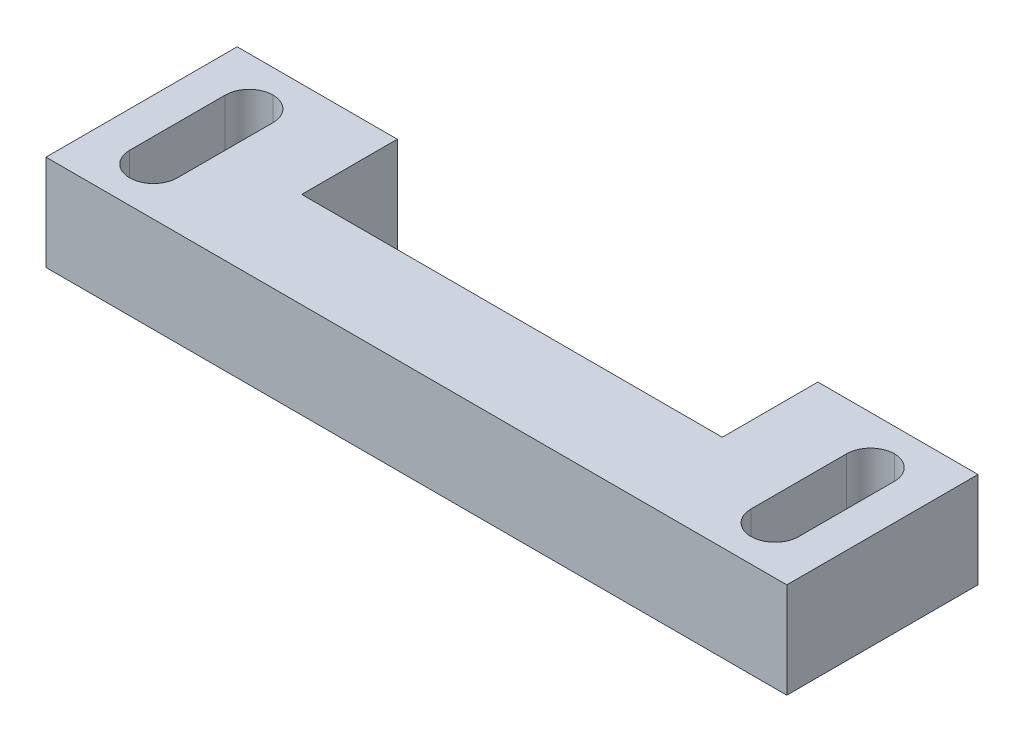
SolidWorks part; units mm, degrees
material "6061 Alloy"
ref_plane "Front Plane" through (0, 0, 0) normal (0, 0, 1) x (1, 0, 0)
ref_plane "Top Plane" through (0, 0, 0) normal (0, 1, 0) x (1, 0, 0)
ref_plane "Right Plane" through (0, 0, 0) normal (1, 0, 0) x (0, 0, -1)
sketch "Sketch1" plane through (0, 0, 0) normal (0, 0, 1) x (1, 0, 0)
  line L1 (-49.2125, 6.35) -> (49.2125, 6.35)
  line L2 (-49.2125, 6.35) -> (-49.2125, -6.35)
  line L3 (-49.2125, -6.35) -> (49.2125, -6.35)
  line L4 (49.2125, 6.35) -> (49.2125, -6.35)
  dimension "D1" = 49.2125
  dimension "D2" = 49.2125
  dimension "D3" = 6.35
  dimension "D4" = 6.35
extrude "Boss-Extrude1" add sketch "Sketch1" along normal mid plane 25.4
sketch "Sketch2" plane through (0, 6.35, 0) normal (0, 1, 0) x (1, 0, 0)
  line L1 (-44.45, 9.525) -> (-38.1, 9.525)
  line L2 (-44.45, 9.525) -> (-44.45, -9.525)
  line L3 (-44.45, -9.525) -> (-38.1, -9.525)
  line L4 (-38.1, 9.525) -> (-38.1, -9.525)
  line L5 (49.2125, 12.7) -> (-49.2125, 12.7) construction
  line L6 (49.2125, -12.7) -> (-49.2125, -12.7) construction
  dimension "D1" = 38.1
  dimension "D2" = 6.35
  dimension "D3" = 3.175
  dimension "D4" = 3.175
extrude "Cut-Extrude1" cut sketch "Sketch2" against normal up to next
fillet "Fillet1" radius 3.175 1 edges at (-44.45, 0, -9.525) type face fillet first side face at (-44.45, 0, 0) second side face at (-41.275, 0, -9.525)
fillet "Fillet2" radius 3.175 1 edges at (-38.1, 0, -9.525) type face fillet first side face at (-39.6875, 0, -9.525) second side face at (-38.1, 0, 0)
fillet "Fillet3" radius 3.175 1 edges at (-44.45, 0, 9.525) type face fillet first side face at (-44.45, 0, 1.5875) second side face at (-41.275, 0, 9.525)
fillet "Fillet4" radius 3.175 1 edges at (-38.1, 0, 9.525) type face fillet first side face at (-38.1, 0, 1.5875) second side face at (-39.6875, 0, 9.525)
mirror "Mirror1" about plane through (0, 0, 0) normal (1, 0, 0) of "Fillet4", "Fillet3", "Fillet2", "Fillet1", "Cut-Extrude1"
sketch "Sketch5" plane through (0, 6.35, 0) normal (0, 1, 0) x (1, 0, 0)
  line L0 (49.2125, 12.7) -> (-49.2125, 12.7) construction
  line L1 (-27.94, 12.7) -> (27.94, 12.7)
  line L2 (-27.94, 12.7) -> (-27.94, 0)
  line L3 (-27.94, 0) -> (27.94, 0)
  line L4 (27.94, 12.7) -> (27.94, 0)
  dimension "D1" = 12.7
  dimension "D2" = 27.94
  dimension "D3" = 27.94
extrude "Cut-Extrude2" cut sketch "Sketch5" against normal up to next
